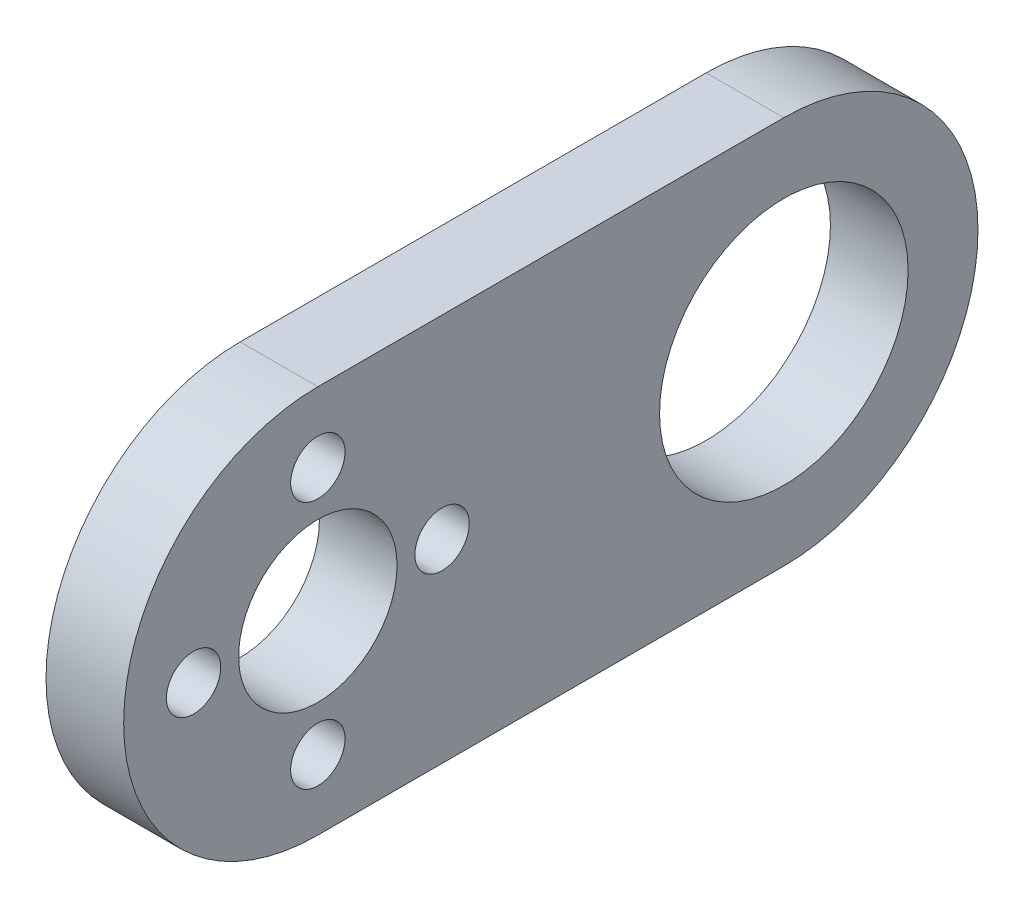
SolidWorks part; units mm, degrees
ref_plane "Alzado" through (0, 0, 0) normal (0, 0, 1) x (1, 0, 0)
ref_plane "Planta" through (0, 0, 0) normal (0, 1, 0) x (1, 0, 0)
ref_plane "Vista lateral" through (0, 0, 0) normal (1, 0, 0) x (0, 0, -1)
sketch "Croquis1" plane through (0, 0, 0) normal (1, 0, 0) x (0, 0, -1)
  line L0 (-27.5, 0) -> (27.5, 0) construction
  line L1 (-15, -12.5) -> (15, -12.5)
  line L2 (-15, 12.5) -> (-15, -12.5) construction
  line L3 (-15, 12.5) -> (15, 12.5)
  line L4 (15, 12.5) -> (15, -12.5) construction
  circle A0 centre (15, 0) radius 8
  circle A1 centre (-15, 0) radius 5.1
  arc A2 (15, 12.5) -> (15, -12.5) centre (15, 0) cw
  arc A3 (-15, -12.5) -> (-15, 12.5) centre (-15, 0) cw
  circle A4 centre (-23, 0) radius 1.75
  circle A5 centre (-15, 8) radius 1.75
  circle A6 centre (-7, 0) radius 1.75
  circle A7 centre (-15, -8) radius 1.75
  point P0 (0, 0)
  point P25 (-15, 0)
  dimension "D3" = 16
  dimension "D5" = 12.5
  dimension "D8" = 15
  dimension "D13" = 8
  dimension "D6" = 12.5
  dimension "D9" = 15
  dimension "D10" = 12.5
  dimension "D4" = 10.2
  dimension "D7" = 12.5
  dimension "D12" = 3.5
  dimension "D1" = 30
  dimension "D2" = 25
  dimension "D11" = 12.5
extrude "Saliente-Extruir1" add sketch "Croquis1" along normal blind 5
